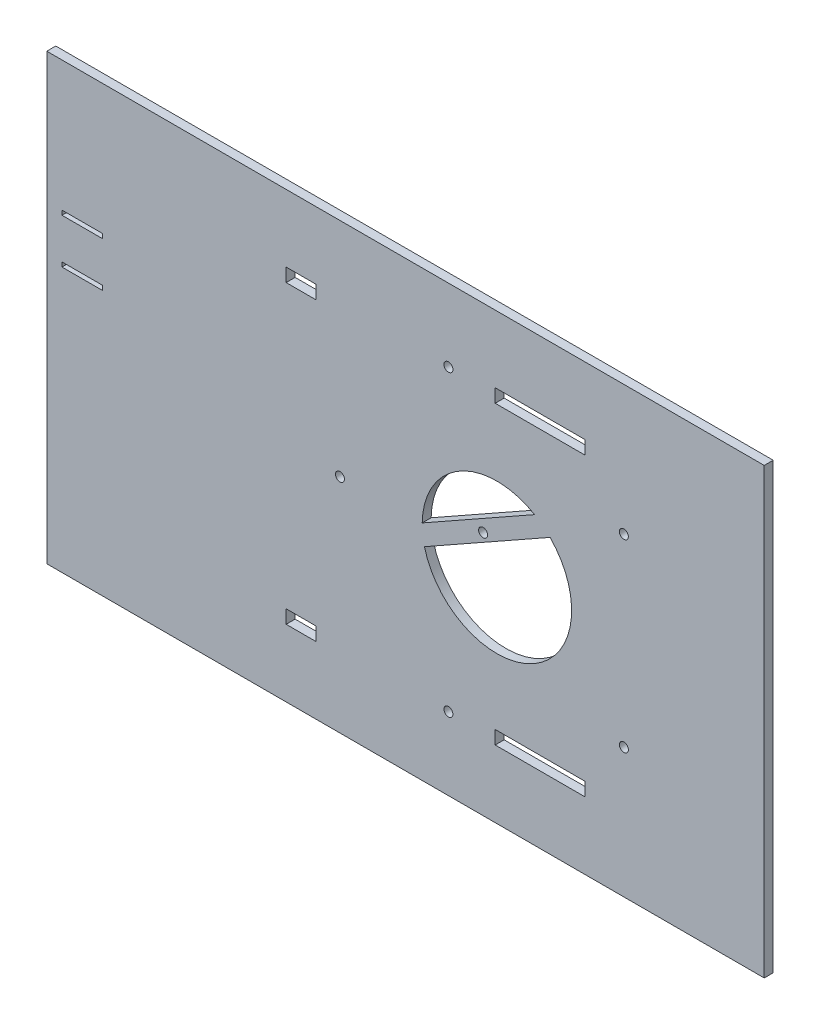
SolidWorks part; units mm, degrees
ref_plane "Front Plane" through (0, 0, 0) normal (0, 0, 1) x (1, 0, 0)
ref_plane "Top Plane" through (0, 0, 0) normal (0, 1, 0) x (1, 0, 0)
ref_plane "Right Plane" through (0, 0, 0) normal (1, 0, 0) x (0, 0, -1)
sketch "Sketch1" plane through (0, 0, 0) normal (0, 0, 1) x (1, 0, 0)
  line L0 (-120.0004, 74.2497) -> (-120.0004, -74.2497)
  line L1 (-120.0004, -74.2497) -> (120.0004, -74.2497)
  line L2 (120.0004, -74.2497) -> (120.0004, 74.2497)
  line L3 (120.0004, 74.2497) -> (-120.0004, 74.2497)
  line L4 (-114.931, 29.2525) -> (-101.4295, 29.2525)
  line L5 (-114.931, 30.7526) -> (-101.4295, 30.7526)
  line L6 (-114.931, 15.751) -> (-101.4295, 15.751)
  line L7 (-114.931, 14.2498) -> (-101.4295, 14.2498)
  line L8 (-39.9319, 51.7498) -> (-39.9319, 47.2493)
  line L9 (-39.9319, 47.2493) -> (-30.0013, 47.2493)
  line L10 (-30.0013, 47.2493) -> (-30.0013, 51.7498)
  line L11 (-30.0013, 51.7498) -> (-39.9319, 51.7498)
  line L12 (29.9987, 51.7498) -> (29.9987, 47.2493)
  line L13 (29.9987, 47.2493) -> (59.9984, 47.2493)
  line L14 (59.9984, 47.2493) -> (59.9984, 51.7498)
  line L15 (59.9984, 51.7498) -> (29.9987, 51.7498)
  line L16 (-39.9319, -47.2483) -> (-30.0013, -47.2483)
  line L17 (-30.0013, -47.2483) -> (-30.0013, -51.7488)
  line L18 (-30.0013, -51.7488) -> (-39.9319, -51.7488)
  line L19 (-39.9319, -51.7488) -> (-39.9319, -47.2483)
  line L20 (30.0002, -47.2483) -> (60.0005, -47.2483)
  line L21 (60.0005, -47.2483) -> (60.0005, -51.7488)
  line L22 (60.0005, -51.7488) -> (30.0002, -51.7488)
  line L23 (30.0002, -51.7488) -> (30.0002, -47.2483)
  line L24 (-101.4295, 29.2525) -> (-101.4295, 30.7526)
  line L25 (-114.931, 30.7526) -> (-114.931, 29.2525)
  line L26 (-114.931, 15.751) -> (-114.931, 14.2498)
  line L27 (-101.4295, 15.751) -> (-101.4295, 14.2498)
  circle A0 centre (30.5702, 0.0013) radius 25
  dimension "D2" = 50
  dimension "D1" = 240.0009
extrude "Boss-Extrude2" add sketch "Sketch1" along normal blind 3
sketch "Sketch2" plane through (0, 0, 3) normal (0, 0, 1) x (1, 0, 0)
  line L0 (42.6692, -21.876) -> (18.107, 21.6731) construction
  line L1 (42.6692, -21.876) -> (27.1636, 5.6157) construction
  line L2 (27.1636, 5.6157) -> (48.3571, 17.569)
  line L3 (48.3571, 17.569) -> (45.3904, 22.8292)
  line L4 (45.3904, 22.8292) -> (3.8383, -0.6066)
  line L5 (3.8383, -0.6066) -> (6.1271, -6.2492)
  line L6 (6.1271, -6.2492) -> (27.1636, 5.6157)
  circle A1 centre (30.5702, 0.0013) radius 25 construction
  circle A2 centre (45.5313, -26.9503) radius 1.5
  circle A3 centre (25.9489, 7.7694) radius 1.5
  point P11 (24.8481, 10.4037)
  point P12 (0, 0)
  point P15 (45.6964, -26.8572)
  point P16 (25.5242, 8.8788)
  point P17 (27.0368, 5.7088)
  point P18 (25.9489, 7.7694)
  dimension "D1" = 3
extrude "Boss-Extrude3" add sketch "Sketch2" against normal blind 3
sketch "Sketch3" plane through (0, 0, 3) normal (0, 0, 1) x (1, 0, 0)
  circle A0 centre (30.5702, 0.0013) radius 52.5
  circle A1 centre (-21.9298, 0.0013) radius 1.5
  circle A2 centre (14.3468, 49.9318) radius 1.5
  circle A3 centre (73.0436, 30.86) radius 1.5
  circle A4 centre (73.0436, -30.8574) radius 1.5
  circle A5 centre (14.3468, -49.9292) radius 1.5
  point P5 (0, 0)
  point P16 (30.5702, 0.0013)
  dimension "D1" = 3
  dimension "D2" = 5
extrude "Cut-Extrude1" cut sketch "Sketch3" against normal blind 3 contours A1
extrude "Cut-Extrude2" cut sketch "Sketch3<3>" against normal blind 3 contours A1 | A5 | A3 | A2 | A4
sketch "Sketch3<3>" plane through (0, 0, 3) normal (0, 0, 1) x (1, 0, 0) same geometry as "Sketch3"
